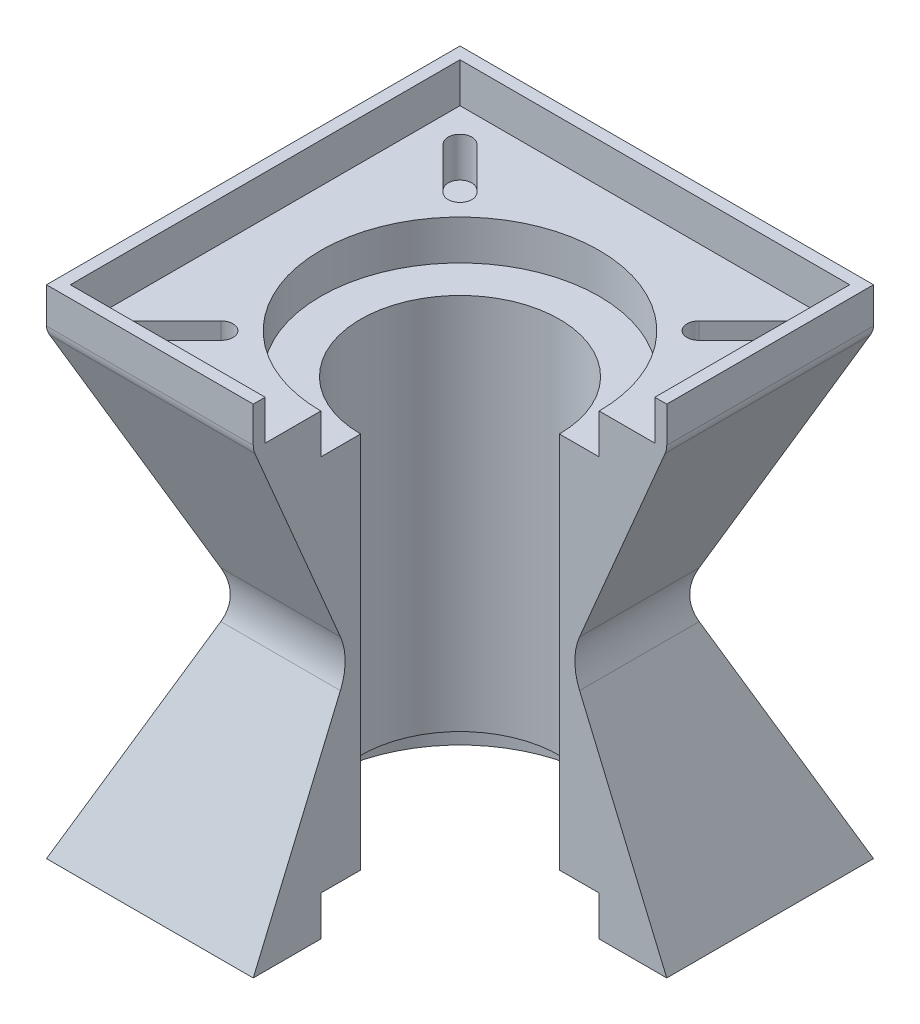
SolidWorks part; units mm, degrees
material "Cast Stainless Steel"
ref_plane "Front Plane" through (0, 0, 0) normal (0, 0, 1) x (1, 0, 0)
ref_plane "Top Plane" through (0, 0, 0) normal (0, 1, 0) x (1, 0, 0)
ref_plane "Right Plane" through (0, 0, 0) normal (1, 0, 0) x (0, 0, -1)
sketch "Sketch1" plane through (0, 0, 0) normal (0, 1, 0) x (1, 0, 0)
  line L1 (-52, 52) -> (52, 52)
  line L2 (-52, 52) -> (-52, -52)
  line L3 (-52, -52) -> (52, -52)
  line L4 (52, 52) -> (52, -52)
  line L5 (-52, 52) -> (52, -52) construction
  line L6 (-52, -52) -> (52, 52) construction
  point P0 (0, 0)
  dimension "D1" = 104
  dimension "D2" = 104
extrude "Boss-Extrude1" add sketch "Sketch1" along normal blind 57.5 draft 23
mirror "Mirror1" about plane through (0, 57.5, 0) normal (0, 1, 0) of bodies 101
sketch "Sketch2" plane through (0, 115, 0) normal (0, 1, 0) x (1, 0, 0)
  circle A0 centre (0, 0) radius 25
  point P3 (0, 0)
  dimension "D1" = 50
extrude "Cut-Extrude2" cut sketch "Sketch2" against normal through all
sketch "Sketch3" plane through (0, 115, 0) normal (0, 1, 0) x (1, 0, 0)
  circle A0 centre (0, 0) radius 35
  dimension "D1" = 70
extrude "Cut-Extrude4" cut sketch "Sketch3" against normal blind 10
sketch "Sketch4" plane through (0, 0, 0) normal (0, -1, 0) x (1, 0, 0)
  circle A0 centre (0, 0) radius 35
  dimension "D1" = 70
extrude "Cut-Extrude5" cut sketch "Sketch4" against normal blind 10
sketch "Sketch5" plane through (0, 115, 0) normal (0, 1, 0) x (1, 0, 0)
  line L0 (0, 55.5964) -> (0, -59.0964) construction
  line L1 (-59.9714, 0) -> (72.6254, 0) construction
  line L3 (0, 0) -> (52, 0)
  line L4 (0, 0) -> (0, -52)
  line L5 (0, -52) -> (52, -52)
  line L6 (52, 0) -> (52, -52)
extrude "Cut-Extrude6" cut sketch "Sketch5" against normal through all
fillet "Fillet1" radius 15 4 edges at (27.5927, 57.5, -13.7963) (0, 57.5, -27.5927) (-27.5927, 57.5, 0) (-13.7963, 57.5, 27.5927)
sketch "Sketch6" plane through (0, 115, 0) normal (0, 1, 0) x (1, 0, 0)
  line L0 (49, 3) -> (49, 0)
  line L1 (52, 0) -> (35, 0) construction
  line L2 (49, 0) -> (52, 0)
  line L8 (0, -49) -> (0, -52)
  line L10 (-3, -49) -> (0, -49)
  line L11 (0, -35) -> (0, -52) construction
  line L12 (-49, -49) -> (-3, -49)
  line L13 (-3, -49) -> (-3, -37.8814)
  line L14 (37.8814, 3) -> (49, 3)
  line L15 (49, 3) -> (49, 49)
  line L16 (49, 49) -> (-49, 49)
  line L17 (-49, 49) -> (-49, -49)
  line L18 (-49, -49) -> (-3, -49)
  line L21 (49, 3) -> (49, 49)
  line L22 (49, 49) -> (-49, 49)
  line L23 (-49, 49) -> (-49, -49)
  line L24 (0, -52) -> (-52, -52)
  line L25 (-52, -52) -> (-52, 52)
  line L26 (-52, 52) -> (52, 52)
  line L27 (52, 52) -> (52, 0)
  arc A2 (37.8814, 3) -> (-3, -37.8814) centre (0, 0) ccw
  dimension "D1" = 3
extrude "Boss-Extrude3" add sketch "Sketch6" along normal blind 10
fillet "Fillet2" radius 5 4 edges at (52, 115, -26) (0, 115, -52) (-52, 115, 0) (-26, 115, 52)
sketch "Sketch7" plane through (0, 115, 0) normal (0, 1, 0) x (1, 0, 0)
  line L0 (0, 55.731) -> (0, -58.4234) construction
  line L1 (-58.4907, 0) -> (64.0099, 0) construction
  line L2 (40.6586, 40.6586) -> (30.052, 30.052) construction
  line L3 (-40.6586, 40.6586) -> (-30.052, 30.052) construction
  line L6 (-38.5373, 42.78) -> (-27.9307, 32.1734)
  line L7 (-42.78, 38.5373) -> (-32.1734, 27.9307)
  line L8 (38.5373, 42.78) -> (27.9307, 32.1734)
  line L9 (42.78, 38.5373) -> (32.1734, 27.9307)
  line L10 (-40.6586, -40.6586) -> (-30.052, -30.052) construction
  line L11 (-38.5373, -42.78) -> (-27.9307, -32.1734)
  line L12 (-42.78, -38.5373) -> (-32.1734, -27.9307)
  circle A2 centre (0, 0) radius 50 construction
  arc A3 (-38.5373, 42.78) -> (-42.78, 38.5373) centre (-40.6586, 40.6586) ccw
  arc A4 (-32.1734, 27.9307) -> (-27.9307, 32.1734) centre (-30.052, 30.052) ccw
  arc A5 (38.5373, 42.78) -> (42.78, 38.5373) centre (40.6586, 40.6586) cw
  arc A6 (32.1734, 27.9307) -> (27.9307, 32.1734) centre (30.052, 30.052) cw
  arc A7 (-38.5373, -42.78) -> (-42.78, -38.5373) centre (-40.6586, -40.6586) cw
  arc A8 (-32.1734, -27.9307) -> (-27.9307, -32.1734) centre (-30.052, -30.052) cw
  point P9 (-35.3553, 35.3553)
  point P14 (0, 0)
  point P15 (0, 0)
  point P16 (0, 0)
  point P17 (0, 0)
  point P20 (35.3553, 35.3553)
  point P27 (-35.3553, -35.3553)
  dimension "D2" = 3
  dimension "D3" = 100
  dimension "D1" = 15
extrude "Cut-Extrude8" cut sketch "Sketch7" against normal blind 10
equation "\"A\"= 115.00mm"
equation "\"B\" = 104mm"
equation "\"C\"= 23deg"
